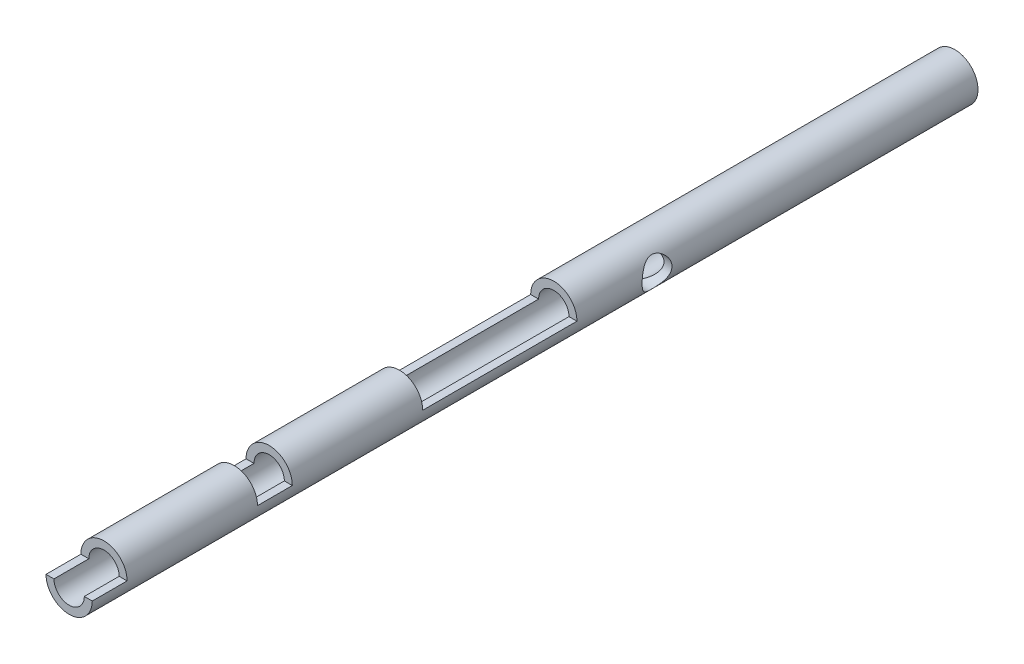
SolidWorks part; units mm, degrees
ref_plane "Front Plane" through (0, 0, 0) normal (0, 0, 1) x (1, 0, 0)
ref_plane "Top Plane" through (0, 0, 0) normal (0, 1, 0) x (1, 0, 0)
ref_plane "Right Plane" through (0, 0, 0) normal (1, 0, 0) x (0, 0, -1)
sketch "Sketch2" plane through (0, 0, 0) normal (0, 0, 1) x (1, 0, 0)
  circle A0 centre (0, 0) radius 4.65
  circle A1 centre (0, 0) radius 3.05
  dimension "D1" = 9.3
  dimension "D2" = 6.1
extrude "Boss-Extrude1" add sketch "Sketch2" against normal blind 178
sketch "Sketch4" plane through (0, 0, 0) normal (1, 0, 0) x (0, 0, -1)
  line L0 (178, 4.65) -> (0, 4.65) construction
  line L1 (0, 0) -> (7, 0)
  line L2 (0, 0) -> (0, 4.65)
  line L3 (0, 4.65) -> (7, 4.65)
  line L4 (7, 0) -> (7, 4.65)
  line L6 (33.2, 0) -> (40.2, 0)
  line L7 (33.2, 0) -> (33.2, 4.65)
  line L8 (33.2, 4.65) -> (40.2, 4.65)
  line L9 (40.2, 0) -> (40.2, 4.65)
  line L10 (66.4, 0) -> (97.4, 0)
  line L11 (66.4, 0) -> (66.4, 4.65)
  line L12 (66.4, 4.65) -> (97.4, 4.65)
  line L13 (97.4, 0) -> (97.4, 4.65)
  dimension "D1" = 7
  dimension "D2" = 7
  dimension "D3" = 26.2
  dimension "D4" = 31
  dimension "D5" = 26.2
extrude "Cut-Extrude1" cut sketch "Sketch4" against normal through all both and the other way through all
sketch "Sketch5" plane through (0, 0, 0) normal (1, 0, 0) x (0, 0, -1)
  line L0 (66.4, 0) -> (66.4, 4.65) construction
  circle A0 centre (113.5, 0) radius 3
  point P4 (0, 0)
  dimension "D1" = 6
  dimension "D2" = 47.1
extrude "Cut-Extrude2" cut sketch "Sketch5" against normal through all both and the other way through all
